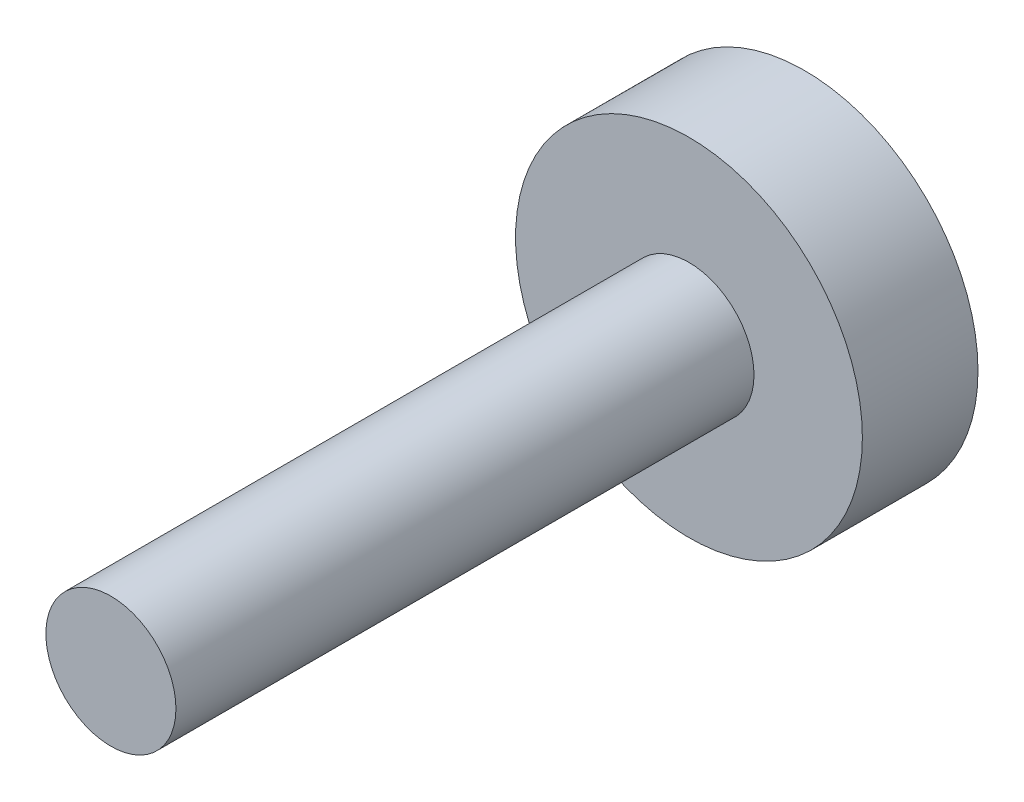
SolidWorks part; units mm, degrees
ref_plane "Front Plane" through (0, 0, 0) normal (0, 0, 1) x (1, 0, 0)
ref_plane "Top Plane" through (0, 0, 0) normal (0, 1, 0) x (1, 0, 0)
ref_plane "Right Plane" through (0, 0, 0) normal (1, 0, 0) x (0, 0, -1)
sketch "Sketch1" plane through (0, 0, 0) normal (0, 0, 1) x (1, 0, 0)
  circle A0 centre (0, 0) radius 1.125
  circle A1 centre (0, 0) radius 3
  dimension "D1" = 6
  dimension "D2" = 2.25
extrude "Boss-Extrude1" add sketch "Sketch1" along normal blind 12 contours A0 region at (0, 0, 0)
extrude "Boss-Extrude2" add sketch "Sketch1<3>" along normal blind 2
sketch "Sketch1<3>" plane through (0, 0, 0) normal (0, 0, 1) x (1, 0, 0) same geometry as "Sketch1"
